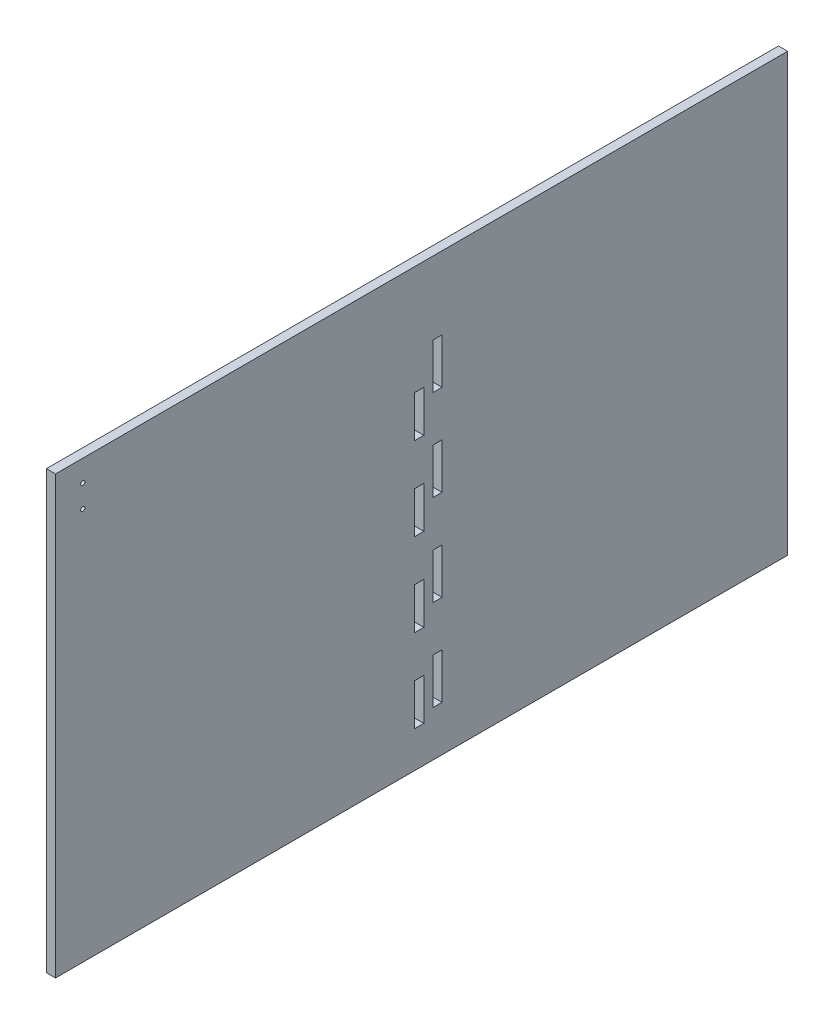
SolidWorks part; units mm, degrees
material "Acrylic (Medium-high impact)"
ref_plane "Front Plane" through (0, 0, 0) normal (0, 0, 1) x (1, 0, 0)
ref_plane "Top Plane" through (0, 0, 0) normal (0, 1, 0) x (1, 0, 0)
ref_plane "Right Plane" through (0, 0, 0) normal (1, 0, 0) x (0, 0, -1)
sketch "Sketch1" plane through (0, 0, 0) normal (1, 0, 0) x (0, 0, -1)
  line L0 (0, 152.4) -> (0, -152.4) construction
  line L1 (-381, 152.4) -> (381, 152.4)
  line L2 (-381, 152.4) -> (-381, -152.4)
  line L3 (-381, -152.4) -> (381, -152.4)
  line L4 (381, 152.4) -> (381, -152.4)
  line L5 (-381, 107.95) -> (-381, 63.5)
  line L10 (-381, 152.4) -> (-387.35, 152.4)
  line L11 (-381, 152.4) -> (-381, 107.95)
  line L12 (-381, 107.95) -> (-387.35, 107.95)
  line L13 (-387.35, 152.4) -> (-387.35, 107.95)
  line L14 (381, 152.4) -> (387.35, 152.4)
  line L15 (381, 152.4) -> (381, 107.95)
  line L16 (381, 107.95) -> (387.35, 107.95)
  line L17 (387.35, 152.4) -> (387.35, 107.95)
  line L18 (-387.35, -152.4) -> (-327.7577, -152.4)
  line L19 (-387.35, -152.4) -> (-387.35, -158.75)
  line L20 (-387.35, -158.75) -> (-327.7577, -158.75)
  line L21 (-327.7577, -152.4) -> (-327.7577, -158.75)
  line L22 (-381, 107.95) -> (-387.35, 107.95)
  line L23 (-387.35, 107.95) -> (-387.35, 63.5)
  line L24 (-381, 63.5) -> (-387.35, 63.5)
  line L25 (381, 107.95) -> (381, 63.5)
  line L26 (381, 107.95) -> (387.35, 107.95)
  line L27 (387.35, 107.95) -> (387.35, 63.5)
  line L28 (381, 63.5) -> (387.35, 63.5)
  line L29 (-381, 63.5) -> (-381, 19.05)
  line L30 (-381, 63.5) -> (-387.35, 63.5)
  line L31 (-387.35, 63.5) -> (-387.35, 19.05)
  line L32 (-381, 19.05) -> (-387.35, 19.05)
  line L33 (381, 63.5) -> (381, 19.05)
  line L34 (381, 63.5) -> (387.35, 63.5)
  line L35 (387.35, 63.5) -> (387.35, 19.05)
  line L36 (381, 19.05) -> (387.35, 19.05)
  line L37 (-381, 19.05) -> (-381, -25.4)
  line L38 (-381, 19.05) -> (-387.35, 19.05)
  line L39 (-387.35, 19.05) -> (-387.35, -25.4)
  line L40 (-381, -25.4) -> (-387.35, -25.4)
  line L41 (381, 19.05) -> (381, -25.4)
  line L42 (381, 19.05) -> (387.35, 19.05)
  line L43 (387.35, 19.05) -> (387.35, -25.4)
  line L44 (381, -25.4) -> (387.35, -25.4)
  line L45 (-381, -25.4) -> (-381, -69.85)
  line L46 (-381, -25.4) -> (-387.35, -25.4)
  line L47 (-387.35, -25.4) -> (-387.35, -69.85)
  line L48 (-381, -69.85) -> (-387.35, -69.85)
  line L49 (381, -25.4) -> (381, -69.85)
  line L50 (381, -25.4) -> (387.35, -25.4)
  line L51 (387.35, -25.4) -> (387.35, -69.85)
  line L52 (381, -69.85) -> (387.35, -69.85)
  line L53 (-381, -69.85) -> (-381, -114.3)
  line L54 (-381, -69.85) -> (-387.35, -69.85)
  line L55 (-387.35, -69.85) -> (-387.35, -114.3)
  line L56 (-381, -114.3) -> (-387.35, -114.3)
  line L57 (381, -69.85) -> (381, -114.3)
  line L58 (381, -69.85) -> (387.35, -69.85)
  line L59 (387.35, -69.85) -> (387.35, -114.3)
  line L60 (381, -114.3) -> (387.35, -114.3)
  line L61 (-381, -114.3) -> (-381, -158.75)
  line L62 (-381, -114.3) -> (-387.35, -114.3)
  line L63 (-387.35, -114.3) -> (-387.35, -158.75)
  line L64 (-381, -158.75) -> (-387.35, -158.75)
  line L65 (381, -114.3) -> (381, -158.75)
  line L66 (381, -114.3) -> (387.35, -114.3)
  line L67 (387.35, -114.3) -> (387.35, -158.75)
  line L68 (381, -158.75) -> (387.35, -158.75)
  line L69 (-327.7577, -158.75) -> (-268.1654, -158.75)
  line L70 (-327.7577, -152.4) -> (-327.7577, -158.75)
  line L71 (-327.7577, -152.4) -> (-268.1654, -152.4)
  line L72 (-268.1654, -152.4) -> (-268.1654, -158.75)
  line L73 (-268.1654, -158.75) -> (-208.5731, -158.75)
  line L74 (-268.1654, -152.4) -> (-268.1654, -158.75)
  line L75 (-268.1654, -152.4) -> (-208.5731, -152.4)
  line L76 (-208.5731, -152.4) -> (-208.5731, -158.75)
  line L77 (-208.5731, -158.75) -> (-148.9808, -158.75)
  line L78 (-208.5731, -152.4) -> (-208.5731, -158.75)
  line L79 (-208.5731, -152.4) -> (-148.9808, -152.4)
  line L80 (-148.9808, -152.4) -> (-148.9808, -158.75)
  line L81 (-148.9808, -158.75) -> (-89.3885, -158.75)
  line L82 (-148.9808, -152.4) -> (-148.9808, -158.75)
  line L83 (-148.9808, -152.4) -> (-89.3885, -152.4)
  line L84 (-89.3885, -152.4) -> (-89.3885, -158.75)
  line L85 (-89.3885, -158.75) -> (-29.7962, -158.75)
  line L86 (-89.3885, -152.4) -> (-89.3885, -158.75)
  line L87 (-89.3885, -152.4) -> (-29.7962, -152.4)
  line L88 (-29.7962, -152.4) -> (-29.7962, -158.75)
  line L89 (-29.7962, -158.75) -> (29.7962, -158.75)
  line L90 (-29.7962, -152.4) -> (-29.7962, -158.75)
  line L91 (-29.7962, -152.4) -> (29.7962, -152.4)
  line L92 (29.7962, -152.4) -> (29.7962, -158.75)
  line L93 (29.7962, -158.75) -> (89.3885, -158.75)
  line L94 (29.7962, -152.4) -> (29.7962, -158.75)
  line L95 (29.7962, -152.4) -> (89.3885, -152.4)
  line L96 (89.3885, -152.4) -> (89.3885, -158.75)
  line L97 (89.3885, -158.75) -> (148.9808, -158.75)
  line L98 (89.3885, -152.4) -> (89.3885, -158.75)
  line L99 (89.3885, -152.4) -> (148.9808, -152.4)
  line L100 (148.9808, -152.4) -> (148.9808, -158.75)
  line L101 (148.9808, -158.75) -> (208.5731, -158.75)
  line L102 (148.9808, -152.4) -> (148.9808, -158.75)
  line L103 (148.9808, -152.4) -> (208.5731, -152.4)
  line L104 (208.5731, -152.4) -> (208.5731, -158.75)
  line L105 (208.5731, -158.75) -> (268.1654, -158.75)
  line L106 (208.5731, -152.4) -> (208.5731, -158.75)
  line L107 (208.5731, -152.4) -> (268.1654, -152.4)
  line L108 (268.1654, -152.4) -> (268.1654, -158.75)
  line L125 (-123.825, 0) -> (123.825, 0) construction
  line L126 (-130.175, 41.956) -> (-123.825, 41.956) construction
  line L127 (-130.175, 41.956) -> (-130.175, -41.956) construction
  line L128 (-130.175, -41.956) -> (-123.825, -41.956) construction
  line L129 (-123.825, 41.956) -> (-123.825, -41.956) construction
  line L138 (123.825, 41.956) -> (130.175, 41.956) construction
  line L139 (123.825, 41.956) -> (123.825, -41.956) construction
  line L140 (123.825, -41.956) -> (130.175, -41.956) construction
  line L141 (130.175, 41.956) -> (130.175, -41.956) construction
  line L143 (268.1654, -158.75) -> (327.7577, -158.75)
  line L144 (268.1654, -152.4) -> (268.1654, -158.75)
  line L145 (268.1654, -152.4) -> (327.7577, -152.4)
  line L146 (327.7577, -152.4) -> (327.7577, -158.75)
  line L147 (327.7577, -158.75) -> (387.35, -158.75)
  line L148 (327.7577, -152.4) -> (327.7577, -158.75)
  line L149 (327.7577, -152.4) -> (387.35, -152.4)
  line L150 (387.35, -152.4) -> (387.35, -158.75)
  point P6 (0, 0)
  point P113 (-127, 41.956)
  point P114 (127, 41.956)
  point P117 (0, 0)
  dimension "D1" = 762
  dimension "D2" = 304.8
  dimension "D3" = 774.7
  dimension "D4" = 311.15
  dimension "D5" = 44.45
  dimension "D7" = 59.5923
  dimension "D9" = 254
  dimension "D10" = 6.35
  dimension "D6" = 7
  dimension "D8" = 13
extrude "Boss-Extrude1" add sketch "Sketch1" along normal blind 6.35 contours L0 L1 L2 L3 | L10 L13 L12 L2 | L56 L63 L18 L2 | L72 L3 L21 L69 | L3 L108 | L4 L67 L60 | L17 L14 L4 L16 | L29 L32 L31 L30 | L45 L48 L47 L46 | L77 L80 L79 L78 | L85 L88 L87 L86 | L93 L96 L95 L94 | L101 L104 L103 L102 | L49 L52 L51 L50 | L33 L36 L35 L34 region at (0, 0, 0) region at (0, 130.175, 384.175) region at (0, 130.175, -384.175) region at (0, -133.35, 384.175) region at (0, -133.35, -384.175) region at (0, -155.575, 297.9615) region at (0, -155.575, -297.9615)
sketch "Sketch3" plane through (6.35, 0, 0) normal (1, 0, 0) x (0, 0, -1)
  line L0 (-130.1762, -127) -> (-130.1762, 76.2) construction
  line L5 (-136.5262, 76.2) -> (-130.1762, 76.2)
  line L6 (-136.5262, 76.2) -> (-136.5262, 47.1714)
  line L7 (-136.5262, 47.1714) -> (-130.1762, 47.1714)
  line L8 (-130.1762, 76.2) -> (-130.1762, 47.1714)
  line L9 (-117.4738, 101.6) -> (-123.8238, 101.6)
  line L10 (-117.4738, 101.6) -> (-117.4738, 69.85)
  line L11 (-117.4738, 69.85) -> (-123.8238, 69.85)
  line L12 (-123.8238, 101.6) -> (-123.8238, 69.85)
  line L13 (-381, -152.4) -> (381, -152.4) construction
  line L14 (-123.8238, -152.4) -> (-123.8238, 101.6) construction
  line L15 (-130.1762, 76.2) -> (-123.8238, 76.2) construction
  line L16 (-127, 41.956) -> (-127, 76.2) construction
  line L17 (-130.175, 41.956) -> (-123.825, 41.956) construction
  line L18 (-117.4738, 69.85) -> (-117.4738, 38.1)
  line L19 (-117.4738, 69.85) -> (-123.8238, 69.85)
  line L20 (-123.8238, 69.85) -> (-123.8238, 38.1)
  line L21 (-117.4738, 38.1) -> (-123.8238, 38.1)
  line L22 (-117.4738, 38.1) -> (-117.4738, 6.35)
  line L23 (-117.4738, 38.1) -> (-123.8238, 38.1)
  line L24 (-123.8238, 38.1) -> (-123.8238, 6.35)
  line L25 (-117.4738, 6.35) -> (-123.8238, 6.35)
  line L26 (-117.4738, 6.35) -> (-117.4738, -25.4)
  line L27 (-117.4738, 6.35) -> (-123.8238, 6.35)
  line L28 (-123.8238, 6.35) -> (-123.8238, -25.4)
  line L29 (-117.4738, -25.4) -> (-123.8238, -25.4)
  line L30 (-117.4738, -25.4) -> (-117.4738, -57.15)
  line L31 (-117.4738, -25.4) -> (-123.8238, -25.4)
  line L32 (-123.8238, -25.4) -> (-123.8238, -57.15)
  line L33 (-117.4738, -57.15) -> (-123.8238, -57.15)
  line L34 (-117.4738, -57.15) -> (-117.4738, -88.9)
  line L35 (-117.4738, -57.15) -> (-123.8238, -57.15)
  line L36 (-123.8238, -57.15) -> (-123.8238, -88.9)
  line L37 (-117.4738, -88.9) -> (-123.8238, -88.9)
  line L38 (-117.4738, -88.9) -> (-117.4738, -120.65)
  line L39 (-117.4738, -88.9) -> (-123.8238, -88.9)
  line L40 (-123.8238, -88.9) -> (-123.8238, -120.65)
  line L41 (-117.4738, -120.65) -> (-123.8238, -120.65)
  line L42 (-136.5262, 47.1714) -> (-136.5262, 18.1429)
  line L43 (-136.5262, 47.1714) -> (-130.1762, 47.1714)
  line L44 (-130.1762, 47.1714) -> (-130.1762, 18.1429)
  line L45 (-136.5262, 18.1429) -> (-130.1762, 18.1429)
  line L46 (-136.5262, 18.1429) -> (-136.5262, -10.8857)
  line L47 (-136.5262, 18.1429) -> (-130.1762, 18.1429)
  line L48 (-130.1762, 18.1429) -> (-130.1762, -10.8857)
  line L49 (-136.5262, -10.8857) -> (-130.1762, -10.8857)
  line L50 (-136.5262, -10.8857) -> (-136.5262, -39.9143)
  line L51 (-136.5262, -10.8857) -> (-130.1762, -10.8857)
  line L52 (-130.1762, -10.8857) -> (-130.1762, -39.9143)
  line L53 (-136.5262, -39.9143) -> (-130.1762, -39.9143)
  line L54 (-136.5262, -39.9143) -> (-136.5262, -68.9429)
  line L55 (-136.5262, -39.9143) -> (-130.1762, -39.9143)
  line L56 (-130.1762, -39.9143) -> (-130.1762, -68.9429)
  line L57 (-136.5262, -68.9429) -> (-130.1762, -68.9429)
  line L58 (-136.5262, -68.9429) -> (-136.5262, -97.9714)
  line L59 (-136.5262, -68.9429) -> (-130.1762, -68.9429)
  line L60 (-130.1762, -68.9429) -> (-130.1762, -97.9714)
  line L61 (-136.5262, -97.9714) -> (-130.1762, -97.9714)
  line L62 (-136.5262, -97.9714) -> (-136.5262, -127)
  line L63 (-136.5262, -97.9714) -> (-130.1762, -97.9714)
  line L64 (-130.1762, -97.9714) -> (-130.1762, -127)
  line L65 (-136.5262, -127) -> (-130.1762, -127)
  line L66 (-117.4738, -120.65) -> (-117.4738, -152.4)
  line L67 (-117.4738, -120.65) -> (-123.8238, -120.65)
  line L68 (-123.8238, -120.65) -> (-123.8238, -152.4)
  line L69 (-117.4738, -152.4) -> (-123.8238, -152.4)
  dimension "D1" = 203.2
  dimension "D2" = 254
  dimension "D3" = 25.4
  dimension "D4" = 6.3525
  dimension "D5" = 6.35
  dimension "D7" = 31.75
  dimension "D9" = 29.0286
  dimension "D6" = 8
  dimension "D8" = 7
extrude "Cut-Extrude1" cut sketch "Sketch3" against normal through all contours L41 L38 L37 L40 | L33 L30 L29 L32 | L25 L22 L21 L24 | L9 L12 L11 L10 | L8 L5 L6 L7 | L46 L49 L48 L45 | L54 L57 L56 L53 | L62 L65 L64 L61 region at (6.35, 61.6857, 133.3512) region at (6.35, 3.6286, 133.3512) region at (6.35, -54.4286, 133.3512) region at (6.35, -112.4857, 133.3512) region at (6.35, 85.725, 120.6488) region at (6.35, 22.225, 120.6488) region at (6.35, -41.275, 120.6488) region at (6.35, -104.775, 120.6488)
sketch "Sketch4" plane through (6.35, 0, 0) normal (1, 0, 0) x (0, 0, -1)
  line L0 (0, 152.4) -> (0, -152.4) construction
  line L1 (-387.35, 152.4) -> (387.35, 152.4) construction
  line L5 (-387.35, 152.4) -> (-387.35, 107.95) construction
  circle A0 centre (-368.3, 137.4) radius 1.5
  circle A1 centre (-368.3, 121.65) radius 1.5
  circle A2 centre (368.3, 137.4) radius 1.5
  circle A3 centre (368.3, 121.65) radius 1.5
  dimension "D1" = 3
  dimension "D2" = 3
  dimension "D3" = 19.05
  dimension "D4" = 15.75
  dimension "D5" = 15
extrude "Cut-Extrude2" cut sketch "Sketch4" against normal up to surface (6.35 mm away) up to face at (0, 22.225, 120.6488)
sketch "Sketch5" plane through (6.35, 0, 0) normal (1, 0, 0) x (0, 0, -1)
  line L0 (-387.35, 63.5) -> (-381, 63.5)
  line L1 (-381, 63.5) -> (-381, 19.05)
  line L2 (-381, 19.05) -> (-387.35, 19.05)
  line L3 (-387.35, 19.05) -> (-387.35, 63.5)
  line L4 (-387.35, -25.4) -> (-381, -25.4)
  line L5 (-381, -25.4) -> (-381, -69.85)
  line L6 (-381, -69.85) -> (-387.35, -69.85)
  line L7 (-387.35, -69.85) -> (-387.35, -25.4)
  line L9 (-208.5731, -152.4) -> (-148.9808, -152.4)
  line L10 (-208.5731, -152.4) -> (-208.5731, -158.75)
  line L11 (-208.5731, -158.75) -> (-148.9808, -158.75)
  line L12 (-148.9808, -152.4) -> (-148.9808, -158.75)
  line L13 (-89.3885, -152.4) -> (-29.7962, -152.4)
  line L14 (-89.3885, -152.4) -> (-89.3885, -158.75)
  line L15 (-89.3885, -158.75) -> (-29.7962, -158.75)
  line L16 (-29.7962, -152.4) -> (-29.7962, -158.75)
  line L17 (29.7962, -152.4) -> (89.3885, -152.4)
  line L18 (29.7962, -152.4) -> (29.7962, -158.75)
  line L19 (29.7962, -158.75) -> (89.3885, -158.75)
  line L20 (89.3885, -152.4) -> (89.3885, -158.75)
  line L21 (148.9808, -152.4) -> (208.5731, -152.4)
  line L22 (148.9808, -152.4) -> (148.9808, -158.75)
  line L23 (148.9808, -158.75) -> (208.5731, -158.75)
  line L24 (208.5731, -152.4) -> (208.5731, -158.75)
  line L25 (387.35, -69.85) -> (381, -69.85)
  line L26 (387.35, -69.85) -> (387.35, -25.4)
  line L27 (387.35, -25.4) -> (381, -25.4)
  line L28 (381, -69.85) -> (381, -25.4)
  line L29 (387.35, 19.05) -> (381, 19.05)
  line L30 (387.35, 19.05) -> (387.35, 63.5)
  line L31 (387.35, 63.5) -> (381, 63.5)
  line L32 (381, 19.05) -> (381, 63.5)
extrude "Cut-Extrude3" cut sketch "Sketch5" against normal up to surface (6.35 mm away) up to face at (0, 121.65, 366.8)
sketch "Sketch6" plane through (6.35, 0, 0) normal (1, 0, 0) x (0, 0, -1)
  line L0 (-387.35, 107.95) -> (-387.35, -114.3)
  line L1 (-387.35, -114.3) -> (-381, -114.3)
  line L2 (-381, -114.3) -> (-381, 107.95)
  line L3 (-381, 107.95) -> (-387.35, 107.95)
  line L16 (387.35, 107.95) -> (387.35, -114.3)
  line L17 (387.35, -114.3) -> (381, -114.3)
  line L18 (381, -114.3) -> (381, 107.95)
  line L19 (381, 107.95) -> (387.35, 107.95)
extrude "Boss-Extrude2" add sketch "Sketch6" against normal up to surface (6.35 mm away) up to face at (0, 121.65, 366.8)
sketch "Sketch7" plane through (6.35, 0, 0) normal (1, 0, 0) x (0, 0, -1)
  line L1 (-387.35, -152.4) -> (387.35, -152.4)
  line L2 (-387.35, -152.4) -> (-387.35, -167.0965)
  line L3 (-387.35, -167.0965) -> (387.35, -167.0965)
  line L4 (387.35, -152.4) -> (387.35, -167.0965)
extrude "Cut-Extrude4" cut sketch "Sketch7" against normal up to surface (6.35 mm away) up to face at (0, -103.7167, 0)
sketch "Sketch8" plane through (6.35, 0, 0) normal (1, 0, 0) x (0, 0, -1)
  line L0 (-387.35, 152.4) -> (387.35, 152.4) construction
  line L1 (123.82, 152.4) -> (387.35, 152.4)
  line L2 (123.82, 152.4) -> (123.82, -152.4)
  line L3 (123.82, -152.4) -> (387.35, -152.4)
  line L4 (387.35, 152.4) -> (387.35, -152.4)
  line L5 (-387.35, 152.4) -> (-387.35, -152.4) construction
  dimension "D1" = 511.17
extrude "Cut-Extrude5" cut sketch "Sketch8" against normal through all
equation "\"Height\"= 12in"
equation "\"Depth\"= 7in"
equation "\"WallThickness\"= 0.25in"
equation "\"FloorThickness\"= 0.25in"
equation "\"D2@Sketch1\"=\"Height\""
equation "\"D3@Sketch1\"=\"D1@Sketch1\"+2*\"WallThickness\""
equation "\"D4@Sketch1\"=\"D2@Sketch1\"+\"FloorThickness\""
equation "\"D5@Sketch1\"=\"D4@Sketch1\"/7"
equation "\"D7@Sketch1\"=\"D3@Sketch1\"/\"D8@Sketch1\""
equation "\"D1@Boss-Extrude1\"=\"WallThickness\""
equation "\"Width\" = 30in"
equation "\"D4@Sketch3\"=\"WallThickness\"+(1/16in)"
equation "\"D5@Sketch3\"=\"WallThickness\""
equation "\"D7@Sketch3\"=\"D2@Sketch3\"/\"D6@Sketch3\""
equation "\"D9@Sketch3\"=\"D1@Sketch3\"/\"D8@Sketch3\""
equation "\"D10@Sketch1\"=\"WallThickness\""
equation "\"D1@Sketch1\"=\"Width\""
